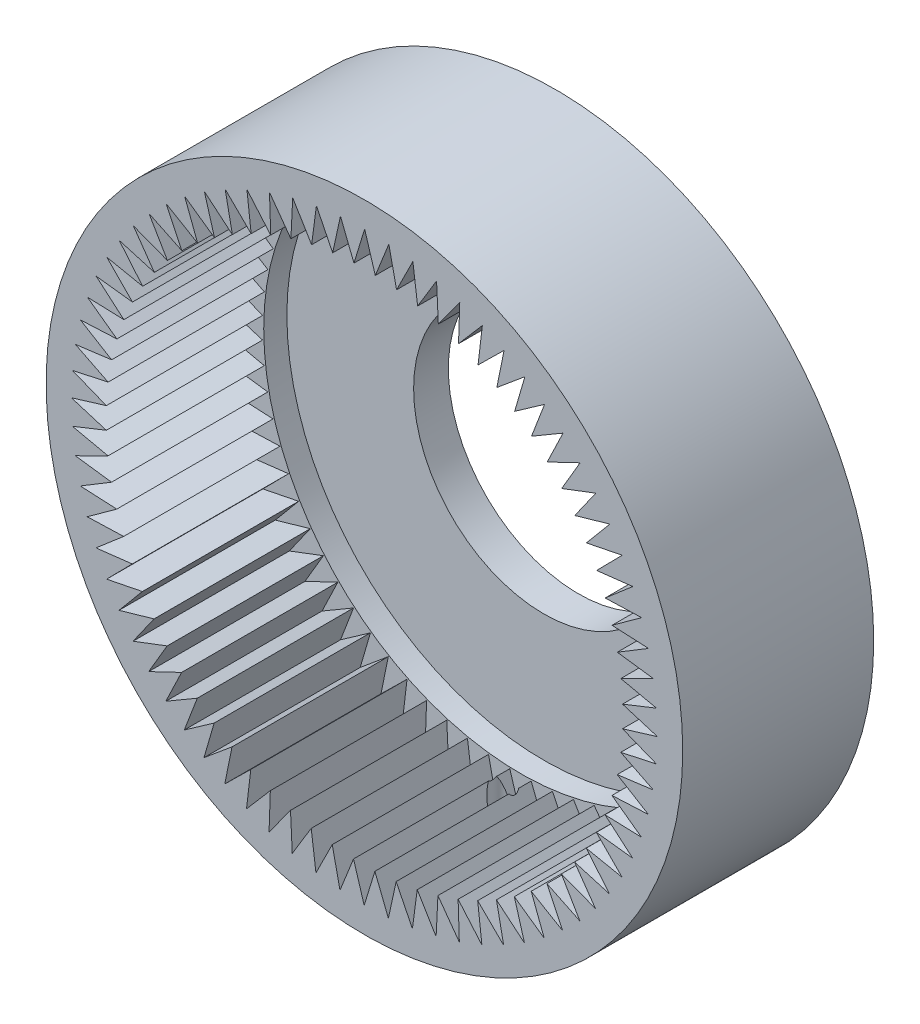
SolidWorks part; units mm, degrees
material "Zoltek Panex 33"
ref_plane "Front Plane" through (0, 0, 0) normal (0, 0, 1) x (1, 0, 0)
ref_plane "Top Plane" through (0, 0, 0) normal (0, 1, 0) x (1, 0, 0)
ref_plane "Right Plane" through (0, 0, 0) normal (1, 0, 0) x (0, 0, -1)
sketch "Sketch1" plane through (0, 0, 0) normal (0, 0, 1) x (1, 0, 0)
  circle A0 centre (0, 0) radius 27.5
  dimension "D1" = 55
extrude "Boss-Extrude1" add sketch "Sketch1" along normal blind 6
sketch "Sketch2" plane through (0, 0, 0) normal (0, 0, 1) x (1, 0, 0)
  circle A0 centre (0, 0) radius 27.5
  dimension "D1" = 55
extrude "Boss-Extrude2" add sketch "Sketch2" along normal blind 4.5 from surface starting at face at (27.5, 0, 6)
sketch "Sketch3" plane through (0, 0, 0) normal (0, 0, 1) x (1, 0, 0)
  circle A0 centre (0, 0) radius 27.5
extrude "Boss-Extrude3" add sketch "Sketch3" along normal blind 6 from surface starting at face at (27.5, 0, 10.5)
sketch "Sketch4" plane through (0, 0, 16.5) normal (0, 0, 1) x (1, 0, 0)
  line L0 (8.2003, -23.949) -> (8.0956, -20.7964)
  line L1 (8.2003, -23.949) -> (7.2077, -21.0502) construction
  line L2 (8.2003, -23.949) -> (6.3506, -21.3939)
  line L3 (6.1946, -24.5444) -> (6.3506, -21.3939)
  line L5 (6.1946, -24.5444) -> (4.5623, -21.8453)
  line L6 (4.1466, -24.9721) -> (4.5623, -21.8453)
  line L7 (4.1466, -24.9721) -> (2.7427, -22.1474)
  line L8 (2.0703, -25.2292) -> (2.7427, -22.1474)
  line L9 (2.0703, -25.2292) -> (0.9044, -22.2983)
  line L10 (-0.0202, -25.314) -> (0.9044, -22.2983)
  line L11 (-0.0202, -25.314) -> (-0.9401, -22.2968)
  line L12 (-2.1106, -25.2259) -> (-0.9401, -22.2968)
  line L13 (-2.1106, -25.2259) -> (-2.7781, -22.143)
  line L14 (-4.1865, -24.9654) -> (-2.7781, -22.143)
  line L15 (-4.1865, -24.9654) -> (-4.5972, -21.838)
  line L16 (-6.2338, -24.5345) -> (-4.5972, -21.838)
  line L17 (-6.2338, -24.5345) -> (-6.3848, -21.3837)
  line L18 (-8.2386, -23.9359) -> (-6.3848, -21.3837)
  line L19 (-8.2386, -23.9359) -> (-8.1289, -20.7835)
  line L20 (-10.1871, -23.1738) -> (-8.1289, -20.7835)
  line L21 (-10.1871, -23.1738) -> (-9.8174, -20.0412)
  line L22 (-12.0659, -22.2534) -> (-9.8174, -20.0412)
  line L23 (-12.0659, -22.2534) -> (-11.4389, -19.162)
  line L24 (-13.8624, -21.181) -> (-11.4389, -19.162)
  line L25 (-13.8624, -21.181) -> (-12.9822, -18.152)
  line L26 (-15.5642, -19.9639) -> (-12.9822, -18.152)
  line L27 (-15.5642, -19.9639) -> (-14.4368, -17.0179)
  line L28 (-17.1596, -18.6104) -> (-14.4368, -17.0179)
  line L29 (-17.1596, -18.6104) -> (-15.7928, -15.7676)
  line L30 (-18.6378, -17.1298) -> (-15.7928, -15.7676)
  line L31 (-18.6378, -17.1298) -> (-17.041, -14.4096)
  line L32 (-19.9887, -15.5322) -> (-17.041, -14.4096)
  line L33 (-19.9887, -15.5322) -> (-18.1727, -12.9531)
  line L34 (-21.2031, -13.8285) -> (-18.1727, -12.9531)
  line L35 (-21.2031, -13.8285) -> (-19.1803, -11.4082)
  line L36 (-22.2726, -12.0304) -> (-19.1803, -11.4082)
  line L37 (-22.2726, -12.0304) -> (-20.0569, -9.7854)
  line L38 (-23.19, -10.15) -> (-20.0569, -9.7854)
  line L39 (-23.19, -10.15) -> (-20.7964, -8.0956)
  line L40 (-23.949, -8.2003) -> (-20.7964, -8.0956)
  line L41 (-23.949, -8.2003) -> (-21.3939, -6.3506)
  line L42 (-24.5444, -6.1946) -> (-21.3939, -6.3506)
  line L43 (-24.5444, -6.1946) -> (-21.8453, -4.5623)
  line L44 (-24.9721, -4.1466) -> (-21.8453, -4.5623)
  line L45 (-24.9721, -4.1466) -> (-22.1474, -2.7427)
  line L46 (-25.2292, -2.0703) -> (-22.1474, -2.7427)
  line L47 (-25.2292, -2.0703) -> (-22.2983, -0.9044)
  line L48 (-25.314, 0.0202) -> (-22.2983, -0.9044)
  line L49 (-25.314, 0.0202) -> (-22.2968, 0.9401)
  line L50 (-25.2259, 2.1106) -> (-22.2968, 0.9401)
  line L51 (-25.2259, 2.1106) -> (-22.143, 2.7781)
  line L52 (-24.9654, 4.1865) -> (-22.143, 2.7781)
  line L53 (-24.9654, 4.1865) -> (-21.838, 4.5972)
  line L54 (-24.5345, 6.2338) -> (-21.838, 4.5972)
  line L55 (-24.5345, 6.2338) -> (-21.3837, 6.3848)
  line L56 (-23.9359, 8.2386) -> (-21.3837, 6.3848)
  line L57 (-23.9359, 8.2386) -> (-20.7835, 8.1289)
  line L58 (-23.1738, 10.1871) -> (-20.7835, 8.1289)
  line L59 (-23.1738, 10.1871) -> (-20.0412, 9.8174)
  line L60 (-22.2534, 12.0659) -> (-20.0412, 9.8174)
  line L61 (-22.2534, 12.0659) -> (-19.162, 11.4389)
  line L62 (-21.181, 13.8624) -> (-19.162, 11.4389)
  line L63 (-21.181, 13.8624) -> (-18.152, 12.9822)
  line L64 (-19.9639, 15.5642) -> (-18.152, 12.9822)
  line L65 (-19.9639, 15.5642) -> (-17.0179, 14.4368)
  line L66 (-18.6104, 17.1596) -> (-17.0179, 14.4368)
  line L67 (-18.6104, 17.1596) -> (-15.7676, 15.7928)
  line L68 (-17.1298, 18.6378) -> (-15.7676, 15.7928)
  line L69 (-17.1298, 18.6378) -> (-14.4096, 17.041)
  line L70 (-15.5322, 19.9887) -> (-14.4096, 17.041)
  line L71 (-15.5322, 19.9887) -> (-12.9531, 18.1727)
  line L72 (-13.8285, 21.2031) -> (-12.9531, 18.1727)
  line L73 (-13.8285, 21.2031) -> (-11.4082, 19.1803)
  line L74 (-12.0304, 22.2726) -> (-11.4082, 19.1803)
  line L75 (-12.0304, 22.2726) -> (-9.7854, 20.0569)
  line L76 (-10.15, 23.19) -> (-9.7854, 20.0569)
  line L77 (-10.15, 23.19) -> (-8.0956, 20.7964)
  line L78 (-8.2003, 23.949) -> (-8.0956, 20.7964)
  line L79 (-8.2003, 23.949) -> (-6.3506, 21.3939)
  line L80 (-6.1946, 24.5444) -> (-6.3506, 21.3939)
  line L81 (-6.1946, 24.5444) -> (-4.5623, 21.8453)
  line L82 (-4.1466, 24.9721) -> (-4.5623, 21.8453)
  line L83 (-4.1466, 24.9721) -> (-2.7427, 22.1474)
  line L84 (-2.0703, 25.2292) -> (-2.7427, 22.1474)
  line L85 (-2.0703, 25.2292) -> (-0.9044, 22.2983)
  line L86 (0.0202, 25.314) -> (-0.9044, 22.2983)
  line L87 (0.0202, 25.314) -> (0.9401, 22.2968)
  line L88 (2.1106, 25.2259) -> (0.9401, 22.2968)
  line L89 (2.1106, 25.2259) -> (2.7781, 22.143)
  line L90 (4.1865, 24.9654) -> (2.7781, 22.143)
  line L91 (4.1865, 24.9654) -> (4.5972, 21.838)
  line L92 (6.2338, 24.5345) -> (4.5972, 21.838)
  line L93 (6.2338, 24.5345) -> (6.3848, 21.3837)
  line L94 (8.2386, 23.9359) -> (6.3848, 21.3837)
  line L95 (8.2386, 23.9359) -> (8.1289, 20.7835)
  line L96 (10.1871, 23.1738) -> (8.1289, 20.7835)
  line L97 (10.1871, 23.1738) -> (9.8174, 20.0412)
  line L98 (12.0659, 22.2534) -> (9.8174, 20.0412)
  line L99 (12.0659, 22.2534) -> (11.4389, 19.162)
  line L100 (13.8624, 21.181) -> (11.4389, 19.162)
  line L101 (13.8624, 21.181) -> (12.9822, 18.152)
  line L102 (15.5642, 19.9639) -> (12.9822, 18.152)
  line L103 (15.5642, 19.9639) -> (14.4368, 17.0179)
  line L104 (17.1596, 18.6104) -> (14.4368, 17.0179)
  line L105 (17.1596, 18.6104) -> (15.7928, 15.7676)
  line L106 (18.6378, 17.1298) -> (15.7928, 15.7676)
  line L107 (18.6378, 17.1298) -> (17.041, 14.4096)
  line L108 (19.9887, 15.5322) -> (17.041, 14.4096)
  line L109 (19.9887, 15.5322) -> (18.1727, 12.9531)
  line L110 (21.2031, 13.8285) -> (18.1727, 12.9531)
  line L111 (21.2031, 13.8285) -> (19.1803, 11.4082)
  line L112 (22.2726, 12.0304) -> (19.1803, 11.4082)
  line L113 (22.2726, 12.0304) -> (20.0569, 9.7854)
  line L114 (23.19, 10.15) -> (20.0569, 9.7854)
  line L115 (23.19, 10.15) -> (20.7964, 8.0956)
  line L116 (23.949, 8.2003) -> (20.7964, 8.0956)
  line L117 (23.949, 8.2003) -> (21.3939, 6.3506)
  line L118 (24.5444, 6.1946) -> (21.3939, 6.3506)
  line L119 (24.5444, 6.1946) -> (21.8453, 4.5623)
  line L120 (24.9721, 4.1466) -> (21.8453, 4.5623)
  line L121 (24.9721, 4.1466) -> (22.1474, 2.7427)
  line L122 (25.2292, 2.0703) -> (22.1474, 2.7427)
  line L123 (25.2292, 2.0703) -> (22.2983, 0.9044)
  line L124 (25.314, -0.0202) -> (22.2983, 0.9044)
  line L125 (25.314, -0.0202) -> (22.2968, -0.9401)
  line L126 (25.2259, -2.1106) -> (22.2968, -0.9401)
  line L127 (25.2259, -2.1106) -> (22.143, -2.7781)
  line L128 (24.9654, -4.1865) -> (22.143, -2.7781)
  line L129 (24.9654, -4.1865) -> (21.838, -4.5972)
  line L130 (24.5345, -6.2338) -> (21.838, -4.5972)
  line L131 (24.5345, -6.2338) -> (21.3837, -6.3848)
  line L132 (23.9359, -8.2386) -> (21.3837, -6.3848)
  line L133 (23.9359, -8.2386) -> (20.7835, -8.1289)
  line L134 (23.1738, -10.1871) -> (20.7835, -8.1289)
  line L135 (23.1738, -10.1871) -> (20.0412, -9.8174)
  line L136 (22.2534, -12.0659) -> (20.0412, -9.8174)
  line L137 (22.2534, -12.0659) -> (19.162, -11.4389)
  line L138 (21.181, -13.8624) -> (19.162, -11.4389)
  line L139 (21.181, -13.8624) -> (18.152, -12.9822)
  line L140 (19.9639, -15.5642) -> (18.152, -12.9822)
  line L141 (19.9639, -15.5642) -> (17.0179, -14.4368)
  line L142 (18.6104, -17.1596) -> (17.0179, -14.4368)
  line L143 (18.6104, -17.1596) -> (15.7676, -15.7928)
  line L144 (17.1298, -18.6378) -> (15.7676, -15.7928)
  line L145 (17.1298, -18.6378) -> (14.4096, -17.041)
  line L146 (15.5322, -19.9887) -> (14.4096, -17.041)
  line L147 (15.5322, -19.9887) -> (12.9531, -18.1727)
  line L148 (13.8285, -21.2031) -> (12.9531, -18.1727)
  line L149 (13.8285, -21.2031) -> (11.4082, -19.1803)
  line L150 (12.0304, -22.2726) -> (11.4082, -19.1803)
  line L151 (12.0304, -22.2726) -> (9.7854, -20.0569)
  line L152 (10.15, -23.19) -> (9.7854, -20.0569)
  line L153 (10.15, -23.19) -> (8.0956, -20.7964)
  line L184 (7.2077, -21.0502) -> (8.5243, -24.8951) construction
  point P235 (0, 0)
  dimension "D1" = 17
  dimension "D2" = 76
extrude "Cut-Extrude1" cut sketch "Sketch4" against normal blind 13.5 contours L0 L153 L152 L151 L150 L149 L148 L147 L146 L145 L144 L143 L142 L141 L140 L139 L138 L137 L136 L135 L134 L133 L132 L131 L130 L129 L128 L127 L126 L125 L124 L123 L122 L121 L120 L119 L118 L117 L116 L115 L114 L113 L112 L111 L110 L109 L108 L107 L106 L105 L104 L103 L102 L101 L100 L99 L98 L97 L96 L95 L94 L93 L92 L91 L90 L89 L88 L87 L86 L85 L84 L83 L82 L81 L80 L79 L78 L77 L76 L75 L74 L73 L72 L71 L70 L69 L68 L67 L66 L65 L64 L63 L62 L61 L60 L59 L58 L57 L56 L55 L54 L53 L52 L51 L50 L49 L48 L47 L46 L45 L44 L43 L42 L41 L40 L39 L38 L37 L36 L35 L34 L33 L32 L31 L30 L29 L28 L27 L26 L25 L24 L23 L22 L21 L20 L19 L18 L17 L16 L15 L14 L13 L12 L11 L10 L9 L8 L7 L6 L5 L3 L2
sketch "Sketch9" [suppressed] plane through (0, 0, 0) normal (0, 0, 1) x (1, 0, 0)
  circle A0 centre (0, 27.1353) radius 1
  dimension "D1" = 2
extrude "Cut-Extrude9" [suppressed] cut sketch "Sketch9" against normal through all from surface
sketch "Sketch10" plane through (0, 0, 0) normal (0, 0, 1) x (1, 0, 0)
  circle A0 centre (0, 0) radius 23
  dimension "D1" = 46
extrude "Boss-Extrude4" add sketch "Sketch10" against normal blind 2 from surface starting at face at (27.5, 0, 0)
sketch "Sketch6" plane through (0, 0, 0) normal (0, 0, 1) x (1, 0, 0)
  circle A0 centre (0, 0) radius 11.25
  dimension "D1" = 22.5
extrude "Cut-Extrude7" cut sketch "Sketch6" against normal through all from surface starting at face at (27.5, 0, 16.5)
sketch "Sketch11" plane through (0, 0, 0) normal (0, 0, 1) x (1, 0, 0)
  circle A0 centre (0, 0) radius 22.2
  dimension "D1" = 44.4
extrude "Cut-Extrude10" cut sketch "Sketch11" against normal blind 2 from surface starting at face at (-11.25, 0, 3)
sketch "Sketch12" plane through (0, 0, 0) normal (0, 1, 0) x (1, 0, 0)
  line L0 (-22.2, -1) -> (22.2, -1) construction
  circle A0 centre (0, -4.5) radius 1
  dimension "D1" = 2
  dimension "D2" = 3.5
extrude "Cut-Extrude11" cut sketch "Sketch12" against normal through all
sketch "Sketch13" plane through (0, 0, 0) normal (0, 0, 1) x (1, 0, 0)
  circle A0 centre (0, -16.58) radius 3.5
  dimension "D1" = 7
  dimension "D2" = 16.58
extrude "Cut-Extrude12" cut sketch "Sketch13" against normal through all
